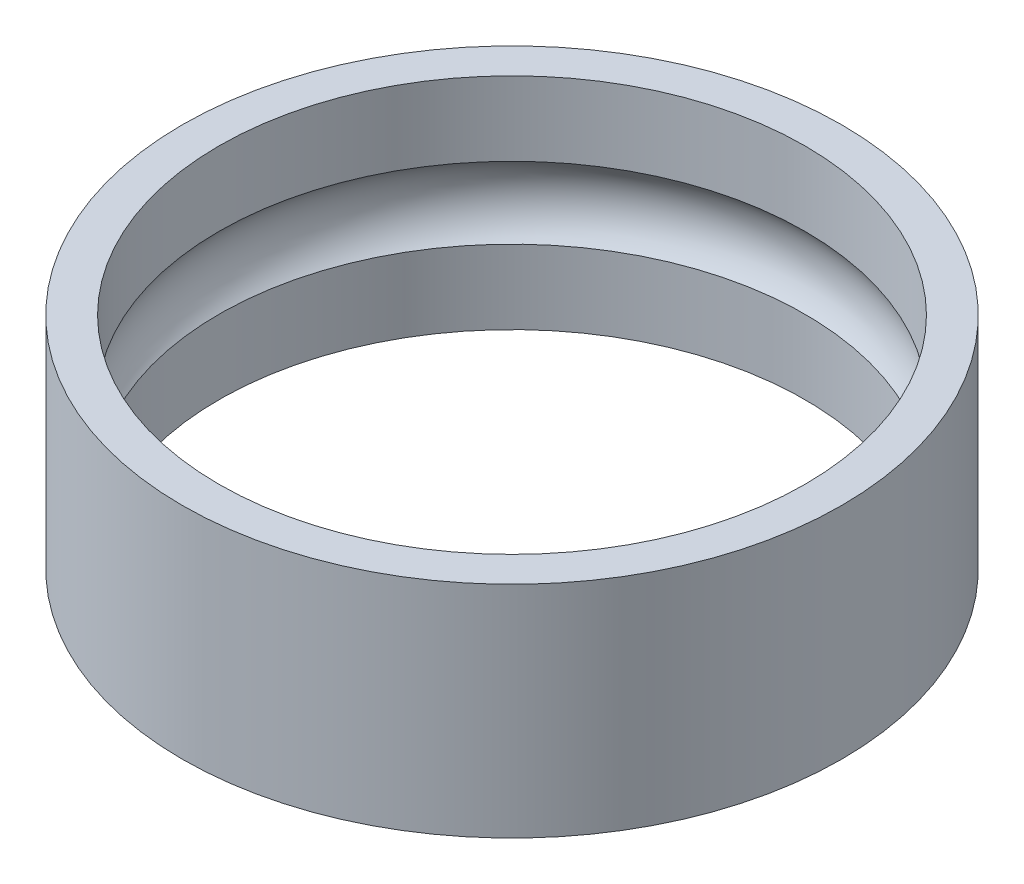
SolidWorks part; units mm, degrees
material "Chrome Stainless Steel"
ref_plane "Front Plane" through (0, 0, 0) normal (0, 0, 1) x (1, 0, 0)
ref_plane "Top Plane" through (0, 0, 0) normal (0, 1, 0) x (1, 0, 0)
ref_plane "Right Plane" through (0, 0, 0) normal (1, 0, 0) x (0, 0, -1)
sketch "DiaProfileS" plane through (0, 0, 0) normal (0, 1, 0) x (1, 0, 0)
  circle A0 centre (0, 0) radius 4
  circle A1 centre (0, 0) radius 4.5
  dimension "InnerDia" = 8
  dimension "Thickness" = 0.5
extrude "DiaProfile" add sketch "DiaProfileS" along normal mid plane 3
sketch "BearingPathProfileS" plane through (0, 0, 0) normal (0, 0, 1) x (1, 0, 0)
  line L1 (0, 0) -> (3.5, 0) construction
  circle A0 centre (3.5, 0) radius 0.7
  point P7 (4, 1.5)
  dimension "BallDia" = 1.4
  dimension "YDim" = 0.5
  dimension "RefRadius" = 3.5
revolve "BearingPathProfile" cut sketch "BearingPathProfileS" angle 360 about axis through (0, 1.5, 0) along (0, -1, 0)
